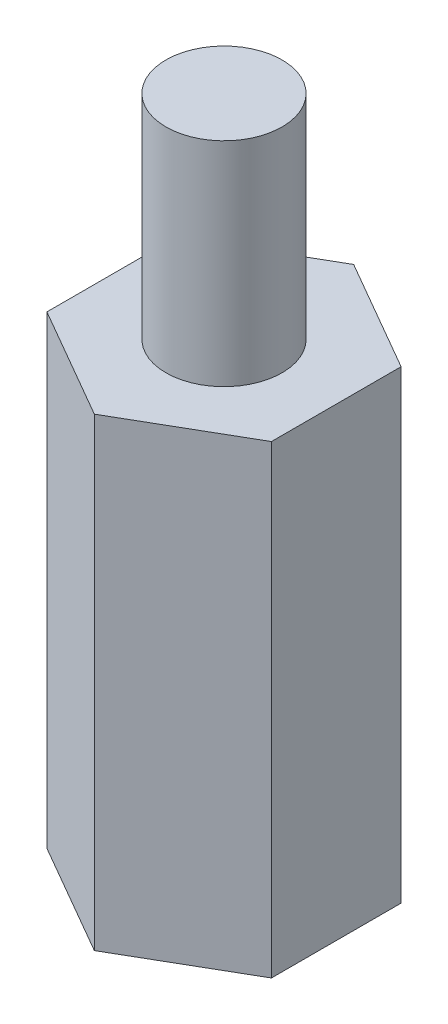
SolidWorks part; units mm, degrees
ref_plane "Front Plane" through (0, 0, 0) normal (0, 0, 1) x (1, 0, 0)
ref_plane "Top Plane" through (0, 0, 0) normal (0, 1, 0) x (1, 0, 0)
ref_plane "Right Plane" through (0, 0, 0) normal (1, 0, 0) x (0, 0, -1)
sketch "Sketch1" plane through (0, 0, 0) normal (0, 1, 0) x (1, 0, 0)
  line L1 (0, -3.3486) -> (2.9, -1.6743)
  line L2 (2.9, -1.6743) -> (2.9, 1.6743)
  line L3 (2.9, 1.6743) -> (0, 3.3486)
  line L4 (0, 3.3486) -> (-2.9, 1.6743)
  line L5 (-2.9, 1.6743) -> (-2.9, -1.6743)
  line L6 (-2.9, -1.6743) -> (0, -3.3486)
  circle A0 centre (0, 0) radius 2.9 construction
  circle A1 centre (0, 0) radius 1.5
  dimension "D2" = 3
  dimension "D1" = 5.8
extrude "Boss-Extrude1" add sketch "Sketch1" along normal mid plane 12
sketch "Sketch2" plane through (0, 6, 0) normal (0, 1, 0) x (1, 0, 0)
  circle A0 centre (0, 0) radius 1.5 construction
  circle A1 centre (0, 0) radius 1.5
extrude "Boss-Extrude2" add sketch "Sketch2" along normal blind 5.5 separate body
